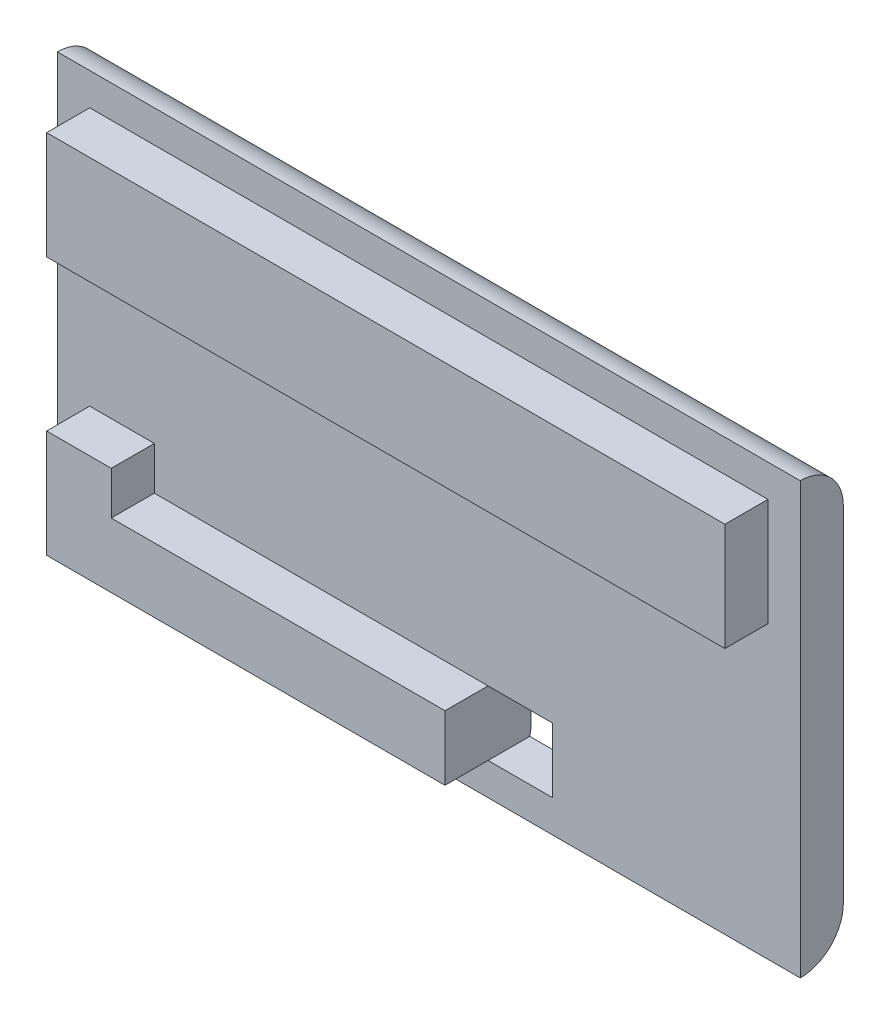
SolidWorks part; units mm, degrees
ref_plane "Ebene vorne" through (0, 0, 0) normal (0, 0, 1) x (1, 0, 0)
ref_plane "Ebene oben" through (0, 0, 0) normal (0, 1, 0) x (1, 0, 0)
ref_plane "Ebene rechts" through (0, 0, 0) normal (1, 0, 0) x (0, 0, -1)
sketch "Sketch1" plane through (0, 0, 0) normal (0, 0, 1) x (1, 0, 0)
  line L1 (-17.25, 10) -> (17.25, 10)
  line L2 (-17.25, 10) -> (-17.25, -10)
  line L3 (-17.25, -10) -> (17.25, -10)
  line L4 (17.25, 10) -> (17.25, -10)
  line L5 (-17.25, 10) -> (17.25, -10) construction
  line L6 (-17.25, -10) -> (17.25, 10) construction
  point P0 (0, 0)
  dimension "D1" = 34.5
  dimension "D2" = 20
extrude "Boss-Extrude1" add sketch "Sketch1" along normal blind 2
sketch "Sketch2" plane through (0, 0, 2) normal (0, 0, 1) x (1, 0, 0)
  line L2 (-17.25, 10) -> (-17.25, -10) construction
  line L3 (-17.25, -10) -> (17.25, -10) construction
  line L4 (17.25, 10) -> (17.25, -10) construction
  line L5 (-17.25, 10) -> (17.25, 10) construction
  line L14 (17.25, 10) -> (-17.25, 10) construction
  line L15 (-17.25, 10) -> (17.25, 10) construction
  line L16 (-17.25, 10) -> (-17.25, 2) construction
  line L18 (-17.25, 2) -> (17.25, 2) construction
  line L19 (17.25, 10) -> (17.25, 2) construction
  line L20 (-15.75, 8.5) -> (-15.75, 3.5)
  line L21 (-15.75, 3.5) -> (15.75, 3.5)
  line L22 (15.75, 8.5) -> (15.75, 3.5)
  line L23 (-15.75, 8.5) -> (15.75, 8.5)
  line L24 (1.1, 0) -> (-1.1, 0) construction
  line L25 (-15.75, -8.5) -> (15.75, -8.5)
  line L26 (15.75, -8.5) -> (15.75, -3.5)
  line L27 (-15.75, -3.5) -> (15.75, -3.5)
  line L28 (-15.75, -8.5) -> (-15.75, -3.5)
  point P0 (0, 0)
  point P7 (-15.25, 8)
  point P8 (-15.25, -8)
  point P9 (15.25, -8)
  point P10 (15.25, 8)
  dimension "D2" = 0
  dimension "D3" = 1.5
  dimension "D1" = 5
extrude "Boss-Extrude2" add sketch "Sketch2" along normal blind 2
sketch "Sketch3" plane through (0, 0, 0) normal (0, 0, -1) x (-1, 0, 0)
  line L0 (15.75, -8.5) -> (-15.75, -8.5) construction
  line L1 (-2.75, -8.5) -> (-5.75, -8.5)
  line L2 (-2.75, -8.5) -> (-2.75, -5.5)
  line L4 (-5.75, -8.5) -> (-5.75, -5.5)
  line L6 (-5.75, -5.5) -> (-2.75, -5.5)
  line L7 (-15.75, -8.5) -> (-15.75, -3.5) construction
  dimension "D1" = 10
  dimension "D3" = 3
extrude "Cut-Extrude1" cut sketch "Sketch3" against normal blind 10
fillet "Fillet1" radius 2 2 edges at (0, -10, 0) (0, 10, 0)
sketch "Sketch4" plane through (0, 0, 4) normal (0, 0, 1) x (1, 0, 0)
  line L0 (15.75, -3.5) -> (-15.75, -3.5) construction
  line L1 (15.75, -8.5) -> (5.75, -8.5)
  line L2 (15.75, -8.5) -> (15.75, -3.5)
  line L3 (15.75, -3.5) -> (5.75, -3.5)
  line L4 (5.75, -8.5) -> (5.75, -5.5)
  line L5 (5.75, -5.5) -> (5.75, -8.5) construction
  line L6 (15.75, -3.5) -> (-15.75, -3.5) construction
  line L7 (-12.75, -3.5) -> (5.75, -3.5)
  line L8 (-12.75, -3.5) -> (-12.75, -5.5)
  line L9 (-12.75, -5.5) -> (5.75, -5.5)
  line L11 (-15.75, -3.5) -> (-15.75, -8.5) construction
  dimension "D1" = 2
  dimension "D2" = 3
extrude "Cut-Extrude2" cut sketch "Sketch4" against normal blind 2
